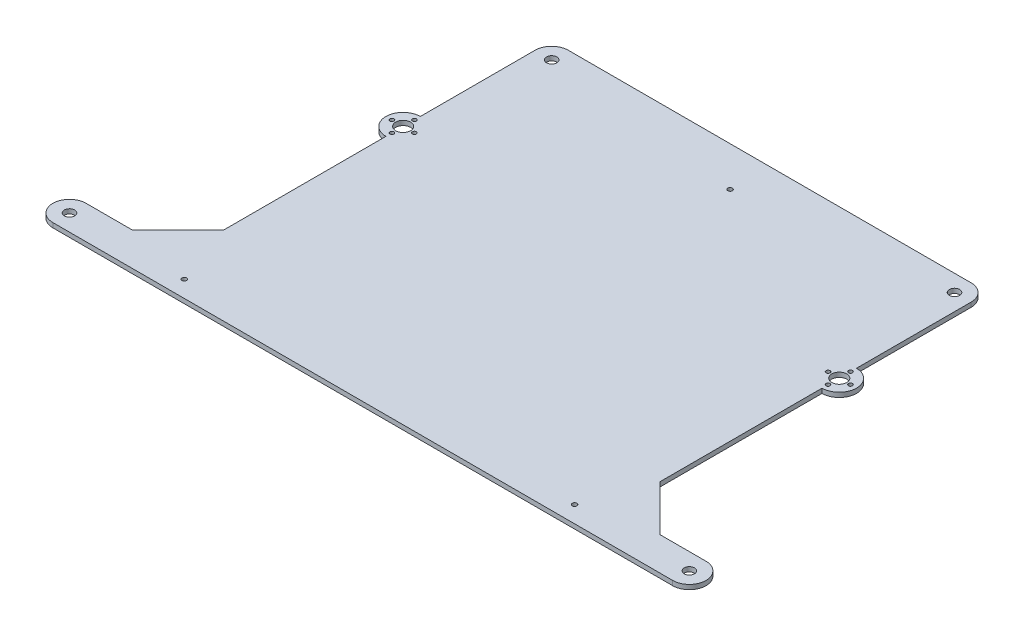
SolidWorks part; units mm, degrees
ref_plane "Front Plane" through (0, 0, 0) normal (0, 0, 1) x (1, 0, 0)
ref_plane "Top Plane" through (0, 0, 0) normal (0, 1, 0) x (1, 0, 0)
ref_plane "Right Plane" through (0, 0, 0) normal (1, 0, 0) x (0, 0, -1)
sketch "Sketch1" plane through (0, 0, 0) normal (0, 1, 0) x (1, 0, 0)
  line L0 (-270, 0) -> (0, 0) construction
  line L1 (-270, -14.5) -> (0, -14.5)
  line L2 (0, 340) -> (0, -14.5)
  line L3 (0, 5.5) -> (-159.9638, 5.5) construction
  line L4 (-159.9638, 5.5) -> (-159.9638, 310) construction
  line L5 (-159.9638, 310) -> (0.0362, 310) construction
  line L6 (-175.5, 384.5) -> (51.2761, 384.5) construction
  line L7 (-175.4638, 340) -> (0, 340)
  line L8 (-189.9638, 325.5) -> (-189.9638, 225.6066)
  line L9 (-229.9638, 14.5) -> (-270, 14.5)
  line L10 (-189.9638, 195.6066) -> (-189.9638, 54.5)
  line L11 (-189.9638, 54.5) -> (-229.9638, 14.5)
  circle A0 centre (-270, 0) radius 4.5
  arc A1 (-270, -14.5) -> (-270, 14.5) centre (-270, 0) cw
  circle A2 centre (-175.4638, 325.5) radius 4.5
  arc A3 (-175.4638, 340) -> (-189.9638, 325.5) centre (-175.4638, 325.5) ccw
  circle A4 centre (-189.9638, 210.6066) radius 6.5
  circle A5 centre (-180.2138, 210.6066) radius 1.75
  circle A6 centre (-189.9638, 220.4066) radius 1.75
  circle A7 centre (-189.9638, 200.8066) radius 1.75
  circle A8 centre (-199.7138, 210.6066) radius 1.75
  arc A9 (-189.9638, 195.6066) -> (-189.9638, 225.6066) centre (-189.9638, 210.6066) cw
  point P18 (-189.9638, 14.5)
  dimension "D2" = 9
  dimension "D3" = 9
  dimension "D7" = 10
  dimension "D10" = 10
  dimension "D13" = 13
  dimension "D14" = 3.5
  dimension "D19" = 15
  dimension "D1" = 270
  dimension "D4" = 160
  dimension "D5" = 304.5
  dimension "D6" = 20
  dimension "D8" = 30
  dimension "D9" = 30
  dimension "D11" = 44.5
  dimension "D12" = 311
  dimension "D15" = 19.5
  dimension "D16" = 9.75
  dimension "D17" = 9.8
  dimension "D18" = 9.8
extrude "Boss-Extrude1" add sketch "Sketch1" along normal blind 4
mirror "Mirror1" about plane through (0, 4, -340) normal (-1, 0, 0) of "Boss-Extrude1"
sketch "Sketch2" plane through (0, 4, 0) normal (0, 1, 0) x (1, 0, 0)
  line L0 (-270, -14.5) -> (270, -14.5) construction
  circle A0 centre (0, 305.5) radius 2
  point P4 (0, -14.5)
  dimension "D1" = 4
  dimension "D2" = 320
extrude "Cut-Extrude1" cut sketch "Sketch2" against normal blind 4
sketch "Sketch3" plane through (0, 4, 0) normal (0, 1, 0) x (1, 0, 0)
  line L0 (-270, -14.5) -> (270, -14.5) construction
  circle A0 centre (-170, 0) radius 2
  circle A1 centre (170, 0) radius 2
  point P6 (0, -14.5)
  point P7 (-170, 14.4922)
  dimension "D1" = 4
  dimension "D2" = 4
  dimension "D3" = 170
  dimension "D4" = 170
  dimension "D5" = 14.5
  dimension "D6" = 14.5
extrude "Cut-Extrude2" cut sketch "Sketch3" against normal blind 10
